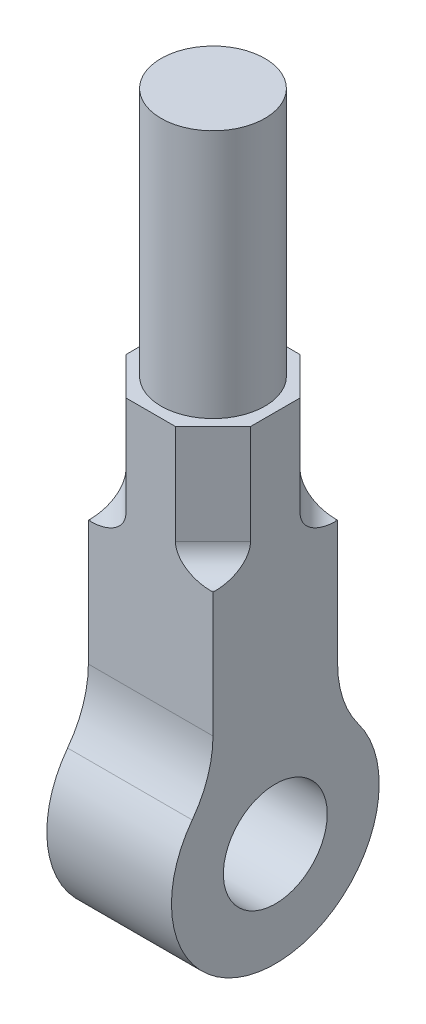
SolidWorks part; units mm, degrees
ref_plane "Front Plane" through (0, 0, 0) normal (1, 0, 0) x (0, 1, 0)
ref_plane "Top Plane" through (0, 0, 0) normal (0, 0, 1) x (0, 1, 0)
ref_plane "Right Plane" through (0, 0, 0) normal (0, 1, 0) x (-1, 0, 0)
sketch "Sketch1" plane through (0, 0, 0) normal (1, 0, 0) x (0, 1, 0)
  line L0 (0, 0) -> (168.7207, 0) construction
  line L2 (60, 30) -> (180, 30)
  line L4 (60, -30) -> (180, -30)
  line L5 (180, 30) -> (180, -30)
  circle A0 centre (0, 0) radius 25
  arc A1 (30, 40) -> (30, -40) centre (0, 0) ccw
  arc A2 (30, -40) -> (60, -30) centre (60, -80) cw
  arc A3 (30, 40) -> (60, 30) centre (60, 80) ccw
  point P12 (40, 30)
  dimension "D1" = 100
  dimension "D2" = 50
  dimension "D5" = 50
  dimension "D3" = 60
  dimension "D4" = 140
extrude "Boss-Extrude1" add sketch "Sketch1" along normal blind 60
sketch "Sketch2" plane through (0, 180, 0) normal (0, 1, 0) x (-1, 0, 0)
  line L0 (-18.06, 30) -> (0, 11.94)
  line L1 (-60, 30) -> (0, 30) construction
  line L2 (0, -30) -> (0, 30) construction
  line L3 (0, 11.94) -> (0, 30)
  line L4 (0, 30) -> (-18.06, 30)
  line L5 (0, -11.94) -> (-18.06, -30)
  line L6 (-18.06, -30) -> (0, -30)
  line L7 (0, -30) -> (0, -11.94)
  line L8 (-41.94, -30) -> (-60, -11.94)
  line L9 (-60, -11.94) -> (-60, -30)
  line L10 (-60, -30) -> (-41.94, -30)
  line L11 (-60, 11.94) -> (-41.94, 30)
  line L12 (-41.94, 30) -> (-60, 30)
  line L13 (-60, 30) -> (-60, 11.94)
  circle A0 centre (-30, 0) radius 25
  line M3 (0, -30) -> (0, 30)
  line M4 (0, 30) -> (-60, 30)
  line M5 (-60, 30) -> (-60, -30)
  line M6 (-60, -30) -> (0, -30)
  dimension "D1" = 50
  dimension "D2" = 30
  dimension "D3" = 18.06
  dimension "D4" = 18.06
  dimension "D5" = 4
extrude "Cut-Extrude3" cut sketch "Sketch2" against normal blind 60 contours L11 M5 M4 | L0 M4 M3 | L5 M3 M6 | L8 M6 M5 region at (6.02, 180, 23.98) region at (53.98, 180, 23.98) region at (6.02, 180, -23.98) region at (53.98, 180, -23.98)
extrude "Boss-Extrude2" add sketch "Sketch2<4>" along normal blind 120 contours A0 region at (30, 180, 0)
sketch "Sketch2<4>" plane through (0, 180, 0) normal (0, 1, 0) x (-1, 0, 0) same geometry as "Sketch2"
fillet "Fillet1" radius 12 4 edges at (9.03, 120, -20.97) (9.03, 120, 20.97) (50.97, 120, -20.97) (50.97, 120, 20.97)
